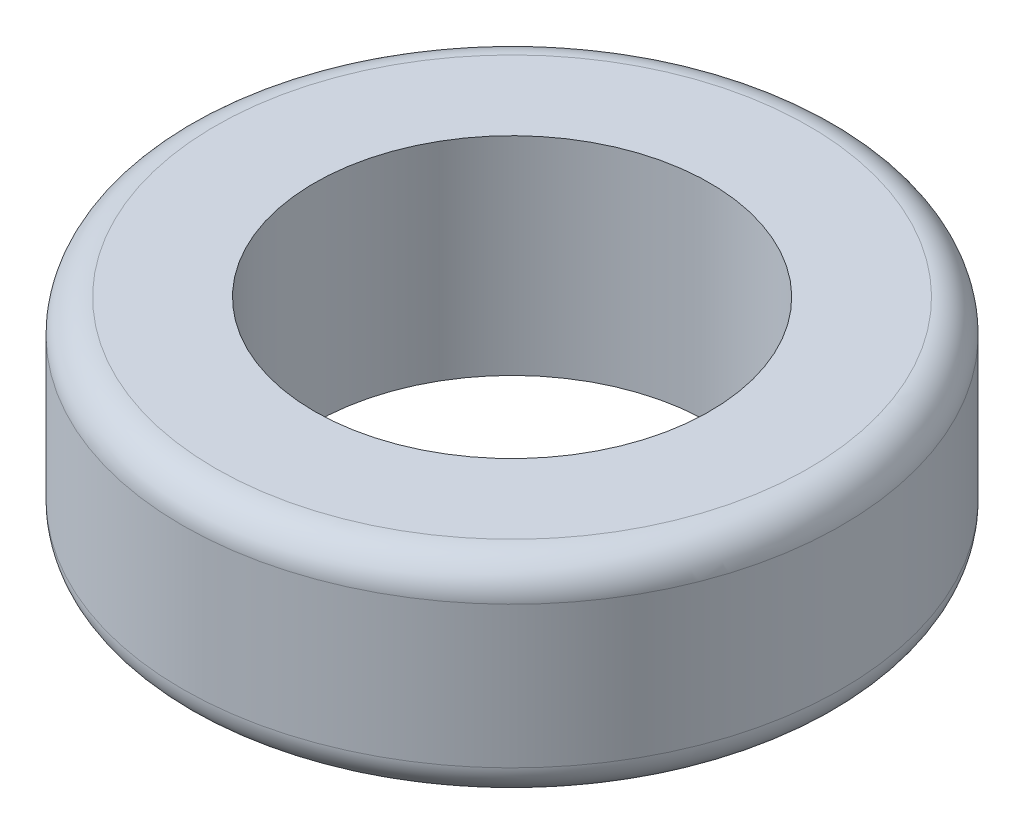
SolidWorks part; units mm, degrees
ref_plane "Front Plane" through (0, 0, 0) normal (0, 0, 1) x (1, 0, 0)
ref_plane "Top Plane" through (0, 0, 0) normal (0, 1, 0) x (1, 0, 0)
ref_plane "Right Plane" through (0, 0, 0) normal (1, 0, 0) x (0, 0, -1)
ref_axis "X-Axis" through (88.99, 0, 0) along (-1, 0, 0)
ref_axis "Y-Axis" through (0, 0, -88.99) along (0, 0, 1)
ref_axis "Z-Axis" through (0, -55, 0) along (0, 1, 0)
sketch "Sketch1" plane through (0, 0, 0) normal (0, 1, 0) x (1, 0, 0)
  circle A0 centre (0, 0) radius 6
  circle A1 centre (0, 0) radius 10
  dimension "D1" = 12
  dimension "D2" = 4
extrude "Boss-Extrude1" add sketch "Sketch1" along normal blind 6.3
fillet "Fillet1" radius 1 2 edges at (0, 0, 10) (0, 6.3, 10)
